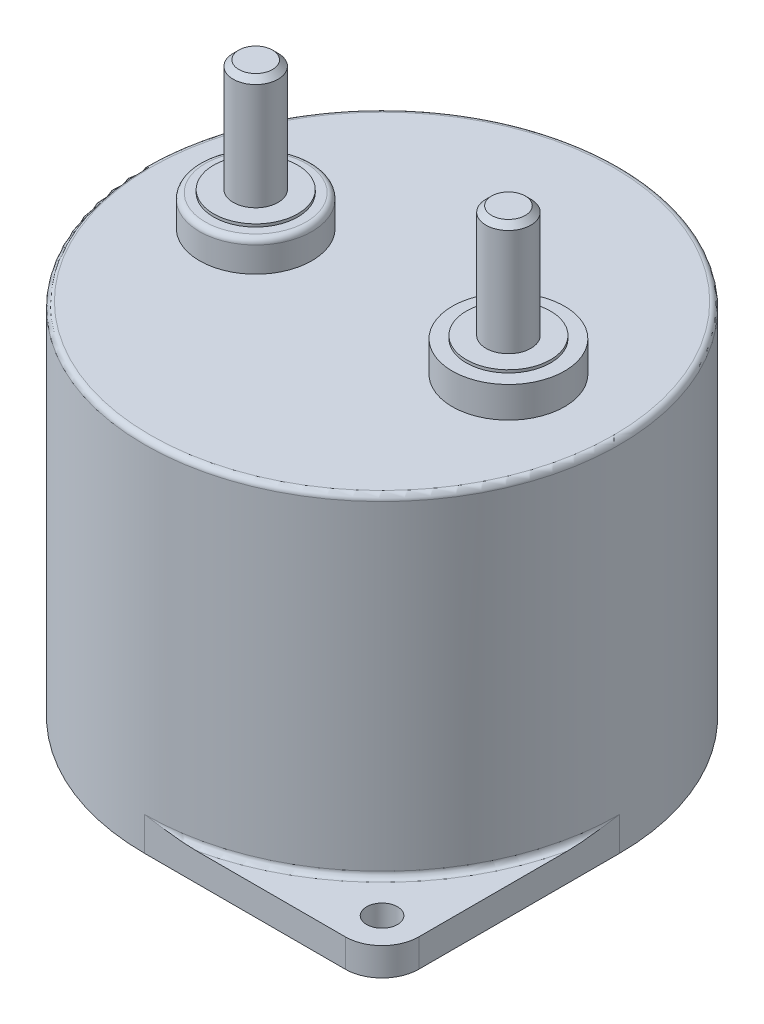
SolidWorks part; units mm, degrees
ref_plane "Front Plane" through (0, 0, 0) normal (0, 0, 1) x (1, 0, 0)
ref_plane "Top Plane" through (0, 0, 0) normal (0, 1, 0) x (1, 0, 0)
ref_plane "Right Plane" through (0, 0, 0) normal (1, 0, 0) x (0, 0, -1)
sketch "Sketch1" plane through (0, 0, 0) normal (0, 1, 0) x (1, 0, 0)
  circle A0 centre (0, 0) radius 42.25
  dimension "D1" = 84.5
extrude "Boss-Extrude1" add sketch "Sketch1" along normal blind 64
sketch "Sketch2" plane through (0, 0, 0) normal (0, -1, 0) x (1, 0, 0)
  line L0 (-35.7089, -35.7089) -> (35.7089, 35.7089) construction
  line L1 (42.25, 0) -> (0, 0) construction
  line L2 (0, 42.25) -> (35.7089, 42.25)
  line L3 (42.25, 35.7089) -> (42.25, 0)
  line L4 (0, -42.25) -> (-35.7089, -42.25)
  line L5 (-42.25, -35.7089) -> (-42.25, 0)
  circle A0 centre (0, 0) radius 42.25 construction
  circle A1 centre (35.7089, 35.7089) radius 2.75
  circle A2 centre (-35.7089, -35.7089) radius 2.75
  arc A3 (-42.25, 0) -> (0, -42.25) centre (0, 0) ccw
  arc A4 (35.7089, 42.25) -> (42.25, 35.7089) centre (35.7089, 35.7089) cw
  arc A5 (-35.7089, -42.25) -> (-42.25, -35.7089) centre (-35.7089, -35.7089) cw
  arc A6 (42.25, 0) -> (0, 42.25) centre (0, 0) ccw
  point P4 (0, 0)
  point P18 (-35.7089, -42.25)
  point P20 (-36.2404, -36.2404)
  point P22 (42.25, 39.1212)
  point P23 (36.4314, 36.4314)
  dimension "D3" = 5.5
  dimension "D1" = 101
  dimension "D2" = 45
extrude "Boss-Extrude2" add sketch "Sketch2" against normal blind 5
sketch "Sketch3" plane through (0, 64, 0) normal (0, 1, 0) x (1, 0, 0)
  line L0 (22.5, 0) -> (-22.5, 0) construction
  circle A0 centre (-22.5, 0) radius 10
  circle A1 centre (22.5, 0) radius 10
  point P3 (-22.5, 0)
  point P7 (0, 0)
  dimension "D1" = 20
  dimension "D2" = 45
extrude "Boss-Extrude3" add sketch "Sketch3" along normal blind 5.5
sketch "Sketch5" plane through (0, 69.5, 0) normal (0, 1, 0) x (1, 0, 0)
  circle A0 centre (-22.5, 0) radius 7.5
  circle A1 centre (22.5, 0) radius 7.5
  dimension "D1" = 15
  dimension "D2" = 15
extrude "Boss-Extrude5" add sketch "Sketch5" along normal offset from surface (0.5 mm away) 6 up to face at (22.5, 64, 10) offset beyond the face yes
sketch "Sketch4" plane through (0, 70, 0) normal (0, 1, 0) x (1, 0, 0)
  circle A0 centre (-22.5, 0) radius 4
  circle A1 centre (22.5, 0) radius 4
  dimension "D1" = 8
extrude "Boss-Extrude4" add sketch "Sketch4" along normal blind 20
fillet "Fillet1" radius 1 4 edges at (0, 64, 42.25) (29.8753, 5, 29.8753) (-29.8753, 5, -29.8753) (-22.5, 69.5, 10)
chamfer "Chamfer1" distance 1 angle 45 2 edges at (-22.5, 90, 4) (22.5, 90, 4)
